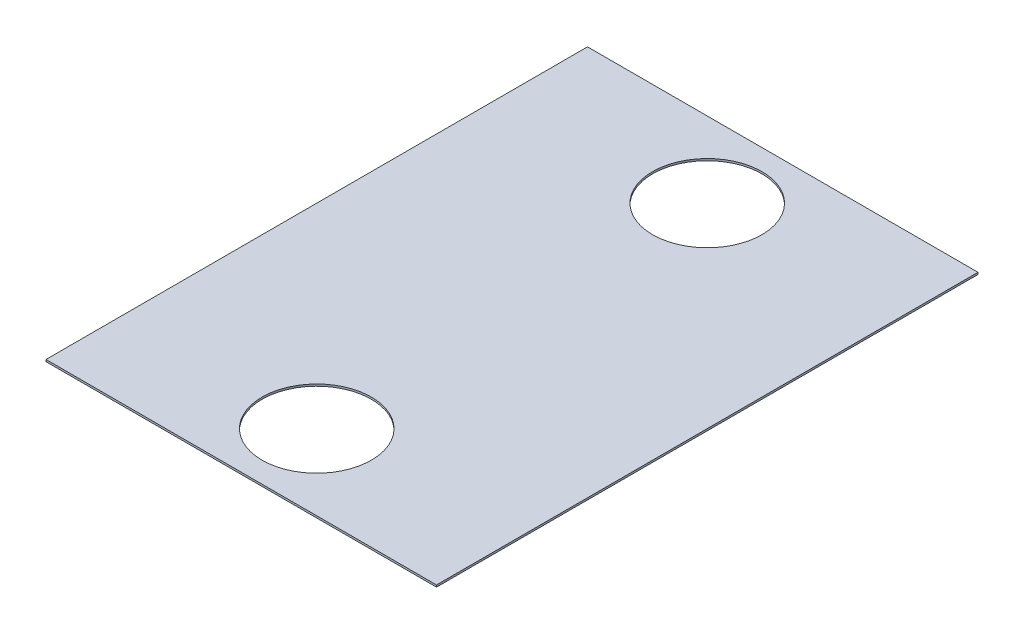
SolidWorks part; units mm, degrees
note: '?' marks a value the reader was unsure of.
ref_plane "Front Plane" through (0, 0, 0) normal (0, 0, 1) x (1, 0, 0)
ref_plane "Top Plane" through (0, 0, 0) normal (0, 1, 0) x (1, 0, 0)
ref_plane "Right Plane" through (0, 0, 0) normal (1, 0, 0) x (0, 0, -1)
sketch "SK_Pan" plane through (0, 0, 0) normal (0, 1, 0) x (1, 0, 0)
  line L1 (-150, 208) -> (150, 208)
  line L2 (-150, 208) -> (-150, -208)
  line L3 (-150, -208) -> (150, -208)
  line L4 (150, 208) -> (150, -208)
  dimension "D1" = 416
  dimension "D2" = 300
  dimension "D3" = 208
  dimension "D4" = 150
base flange "SM_Pan" sketch "SK_Pan" thickness 1.5 reverse thickness direction no parameters "D1"=1.5
sketch "SK_Holes" plane through (0, 0, 0) normal (0, 1, 0) x (1, 0, 0)
  circle A0 centre (0, -150) radius 42
  circle A1 centre (0, 150) radius 42
  dimension "D2" = 84
  dimension "D4" = 84
  dimension "D1" = 150
  dimension "D3" = 150
extrude "CUT_Holes" cut sketch "SK_Holes" along normal blind 1.5
ref_axis "AX_X" through (0, 0, -228.8) along (0, 0, 1)?
ref_axis "AX_Y" through (165, 0, 0) along (-1, 0, 0)?
ref_axis "AX_Z" through (0, 1.575, 0) along (0, -1, 0)?
sketch "Bend-Lines3" [suppressed] plane through (0, 0, 0) normal (0, 1, 0) x (1, 0, 0)
sketch "Bounding-Box3" [suppressed] plane through (0, 0, 0) normal (0, 1, 0) x (1, 0, 0)
sheet metal parameters "Sheet-Metal2" thickness 1.5 parameters "D1"=1.5
flat pattern "Flat-Pattern2" [suppressed]
sketch "Bend-Lines4" plane through (0, 0, 0) normal (0, 1, 0) x (1, 0, 0)
sketch "Bounding-Box4" [suppressed] plane through (0, 0, 0) normal (0, 1, 0) x (1, 0, 0)
sheet metal parameters "Sheet-Metal3" thickness 1.5 parameters "D1"=1.5
flat pattern "Flat-Pattern2"
sketch "Bend-Lines4" plane through (0, 0, 0) normal (0, 1, 0) x (1, 0, 0)
sketch3d "Bounding-Box4" [suppressed]
  line L0 (-150, 208, 0) -> (-150, -208, 0) construction
  line L1 (150, 208, 0) -> (150, -208, 0) construction
  line L2 (-150, 208, 0) -> (150, 208, 0) construction
  line L3 (-150, -208, 0) -> (150, -208, 0) construction
equation "\"BODY_L\"= 420"
equation "\"BODY_W\"= 340"
equation "\"FLOOR_Z\"= 35"
equation "\"DECK_Z\"= 180"
equation "\"DECK_T\"= 2"
equation "\"GRID\"= 20"
equation "\"PROFILE\"= 20"
equation "\"SM_T\"= 1.5"
equation "\"PAN_T\"= 1.5"
equation "\"PAN_TOP\"= \"FLOOR_Z\" + \"PAN_T\""
equation "\"RAIL_Y\"= 140"
equation "\"RAIL_X\"= \"BODY_L\" / 2 - \"PROFILE\" / 2 - 2"
equation "\"BOTRING_Z\"= \"PAN_TOP\" + \"PROFILE\" / 2"
equation "\"TOPRING_Z\"= \"DECK_Z\" - \"DECK_T\" - \"PROFILE\" / 2"
equation "\"DRAWER_Z\"= 93"
equation "\"MIDX_Z\"= \"DRAWER_Z\" - \"SM_T\" - \"PROFILE\" / 2"
equation "\"SKIN_Y\"= \"RAIL_Y\" + \"PROFILE\" / 2"
equation "\"SKIN_T\"= 2"
equation "\"WHEEL_D\"= 144"
equation "\"WHEEL_W\"= 52"
equation "\"TRACK\"= 365"
equation "\"AXLE_Z\"= \"WHEEL_D\" / 2"
equation "\"WHEEL_WEB_OFF\"= 6"
equation "\"HUB_T\"= 8"
equation "\"BUSHING_L\"= 6"
equation "\"HUB_GAP\"= 1"
equation "\"MOTOR_UP\"= 7"
equation "\"MOTOR_FACE_Y\"= \"TRACK\" / 2 + \"WHEEL_WEB_OFF\" - (\"BUSHING_L\" + \"HUB_GAP\" + \"HUB_T\")"
equation "\"MOTOR_AXIS_Z\"= \"AXLE_Z\" + \"MOTOR_UP\""
equation "\"CASTER_D\"= 50"
equation "\"CASTER_X\"= 150"
equation "\"CASTER_H\"= 68"
equation "\"POST_X\"= -40"
equation "\"POST_DY\"= 120"
equation "\"POST_SIZE\"= 20"
equation "\"POST_TOP\"= 400"
equation "\"BRACE_Z\"= 335"
equation "\"STRUT_X0\"= -140"
equation "\"HEAD_X0\"= -110"
equation "\"HEAD_X1\"= 12"
equation "\"BEZEL_T\"= 3"
equation "\"WEDGE_MID\"= 7.7"
equation "\"OAK_D\"= 22.9"
equation "\"HEAD_W\"= 210"
equation "\"HEAD_Z0\"= \"POST_TOP\""
equation "\"HEAD_TOP\"= 525"
equation "\"HEAD_TOP_X\"= -20"
equation "\"SCREEN_ANG\"= 35"
equation "\"LENS_X\"= 45.6"
equation "\"LENS_Z\"= 450"
equation "\"OAK_TILT\"= 5"
equation "\"OAK_VFOV_DEPTH\"= 79.5"
equation "\"OAK_VFOV_RGB\"= 72"
equation "\"LIDAR_X\"= 110"
equation "\"SCAN_Z\"= 260"
equation "\"STRUT_Z\"= \"SCAN_Z\" - 20"
equation "\"LIDAR_SCAN_H\"= 27.2"
equation "\"LIDAR_MOUNT_Z\"= \"SCAN_Z\" - \"LIDAR_SCAN_H\""
equation "\"ESTOP_X\"= -172.5"
equation "\"ESTOP_Y\"= -127.5"
equation "\"ESTOP_TOP\"= 225"
equation "\"BUMPER_T\"= 15"
equation "\"BUMPER_Z0\"= 40"
equation "\"BUMPER_Z1\"= 130"
equation "\"CLIFF_X\"= 218"
equation "\"CLIFF_Y\"= 105"
equation "\"CLIFF_Z\"= 72"
equation "\"CLIFF_ANG\"= 50"
equation "\"CONTACT_X\"= 216"
equation "\"CONTACT_Y\"= 64"
equation "\"CONTACT_Z\"= 30"
equation "\"DOCK_TAG_DIST\"= 250"
equation "\"DOCK_TAG_SIZE\"= 80"
equation "\"DOCK_TAG_Z\"= 400"
equation "\"BAT_L\"= 240"
equation "\"BAT_W\"= 90"
equation "\"BAT_H\"= 58"
equation "\"BAT_Z\"= \"DRAWER_Z\" + \"SM_T\""
equation "\"BAT_X\"= 0"
equation "\"PCB_L\"= 95"
equation "\"PCB_W\"= 120"
equation "\"PCB_H\"= 40"
equation "\"PCB_X\"= 62.5"
equation "\"DRV_X\"= 85"
equation "\"DRV_Y\"= 100"
equation "\"DRV_S\"= 50"
equation "\"COMPUTE_X\"= -65"
equation "\"COMPUTE_L\"= 90"
equation "\"COMPUTE_W\"= 160"
equation "\"D1@SK_Pan\" = 2 * (\"RAIL_X\" + \"PROFILE\" / 2)"
equation "\"D2@SK_Pan\" = 2 * (\"RAIL_Y\" + \"PROFILE\" / 2)"
equation "\"D3@SK_Pan\" = (2 * (\"RAIL_X\" + \"PROFILE\" / 2)) / 2"
equation "\"D4@SK_Pan\" = (2 * (\"RAIL_Y\" + \"PROFILE\" / 2)) / 2"
equation "\"D1@SK_Holes\" = \"CASTER_X\""
equation "\"D3@SK_Holes\" = \"CASTER_X\""
